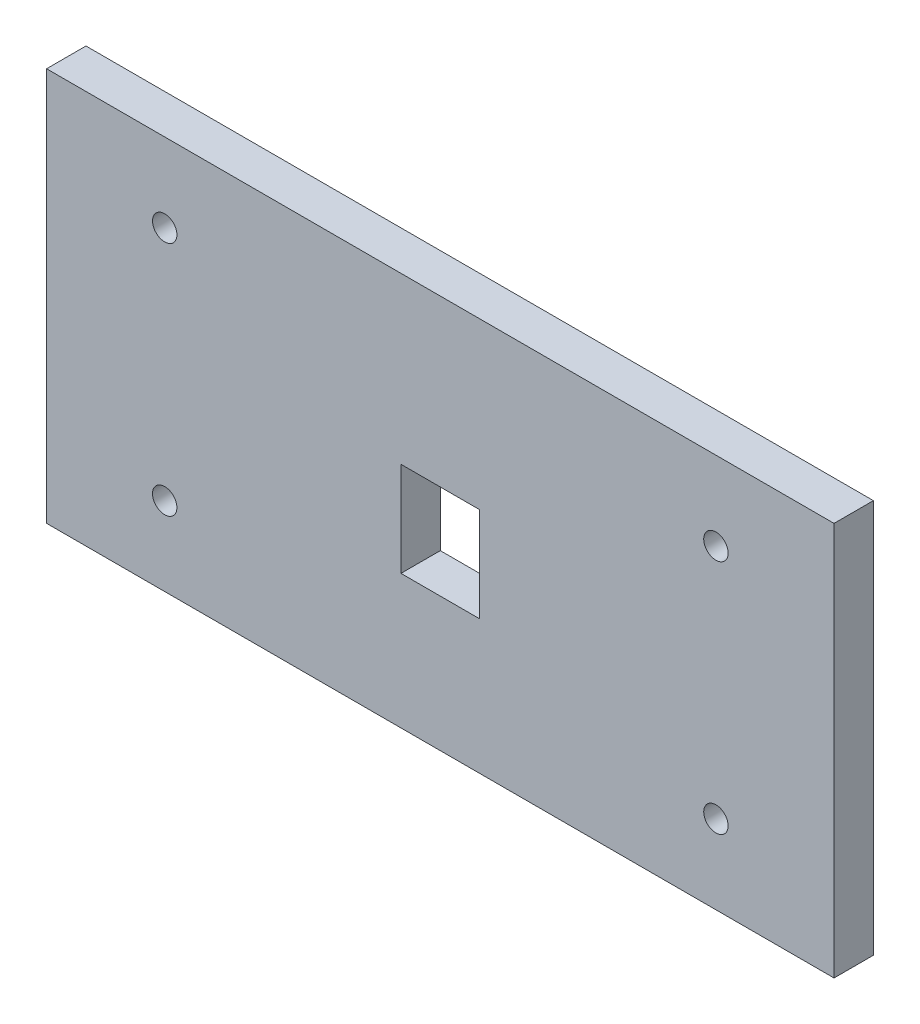
SolidWorks part; units mm, degrees
ref_plane "Plan de face" through (0, 0, 0) normal (0, 0, 1) x (1, 0, 0)
ref_plane "Plan de dessus" through (0, 0, 0) normal (0, 1, 0) x (1, 0, 0)
ref_plane "Plan de droite" through (0, 0, 0) normal (1, 0, 0) x (0, 0, -1)
sketch "Esquisse1" plane through (0, 0, 0) normal (0, 0, 1) x (1, 0, 0)
  line L0 (0, 0) -> (28.085, 0) construction
  line L1 (-50, -25) -> (50, -25)
  line L2 (-50, -25) -> (-50, 25)
  line L3 (-50, 25) -> (50, 25)
  line L4 (50, -25) -> (50, 25)
  line L5 (-50, -25) -> (50, 25) construction
  line L6 (-50, 25) -> (50, -25) construction
  line L7 (0, 0) -> (0, 15.7531) construction
  line L8 (0, 0) -> (0, -2) construction
  line L13 (-5, -8) -> (5, -8)
  line L14 (-5, -8) -> (-5, 4)
  line L15 (-5, 4) -> (5, 4)
  line L16 (5, -8) -> (5, 4)
  line L17 (-5, -8) -> (5, 4) construction
  line L18 (-5, 4) -> (5, -8) construction
  circle A0 centre (-35, -15) radius 1.55
  circle A1 centre (35, -15) radius 1.55
  circle A2 centre (35, 15) radius 1.55
  circle A3 centre (-35, 15) radius 1.55
  point P0 (0, 0)
  point P17 (0, -2)
  dimension "D3" = 3.1
  dimension "D1" = 100
  dimension "D2" = 50
  dimension "D4" = 15
  dimension "D5" = 10
  dimension "D6" = 10
  dimension "D7" = 12
  dimension "D8" = 23
extrude "Boss.-Extru.1" add sketch "Esquisse1" against normal blind 5
